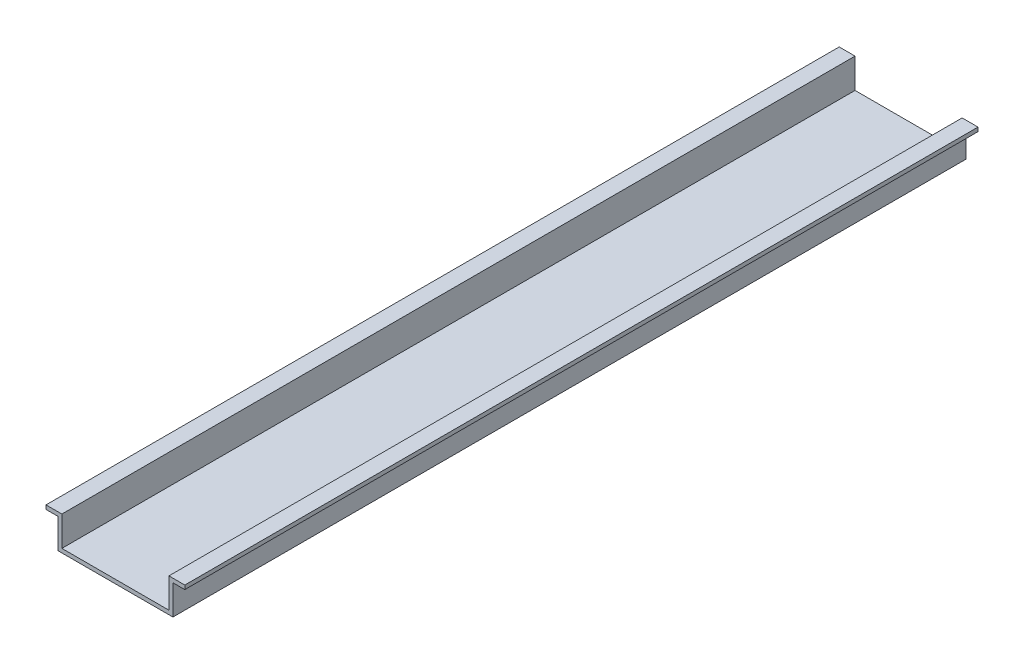
SolidWorks part; units mm, degrees
ref_plane "Front Plane" through (0, 0, 0) normal (0, 0, 1) x (1, 0, 0)
ref_plane "Top Plane" through (0, 0, 0) normal (0, 1, 0) x (1, 0, 0)
ref_plane "Right Plane" through (0, 0, 0) normal (1, 0, 0) x (0, 0, -1)
sketch "Sketch1" plane through (0, 0, 0) normal (0, 0, 1) x (1, 0, 0)
  line L0 (0, 0) -> (0, 18.2991) construction
  line L1 (13.5, 0) -> (-13.5, 0)
  line L2 (-13.5, 0) -> (-13.5, 7.5)
  line L3 (-13.5, 7.5) -> (-17.5, 7.5)
  line L4 (13.5, 7.5) -> (17.5, 7.5)
  line L5 (13.5, 0) -> (13.5, 7.5)
  point P9 (0, 0)
  dimension "D1" = 35
  dimension "D2" = 27
  dimension "D3" = 7.5
extrude "Extrude-Thin1" add sketch "Sketch1" along normal mid plane 200 thin thin type one direction wall 1
